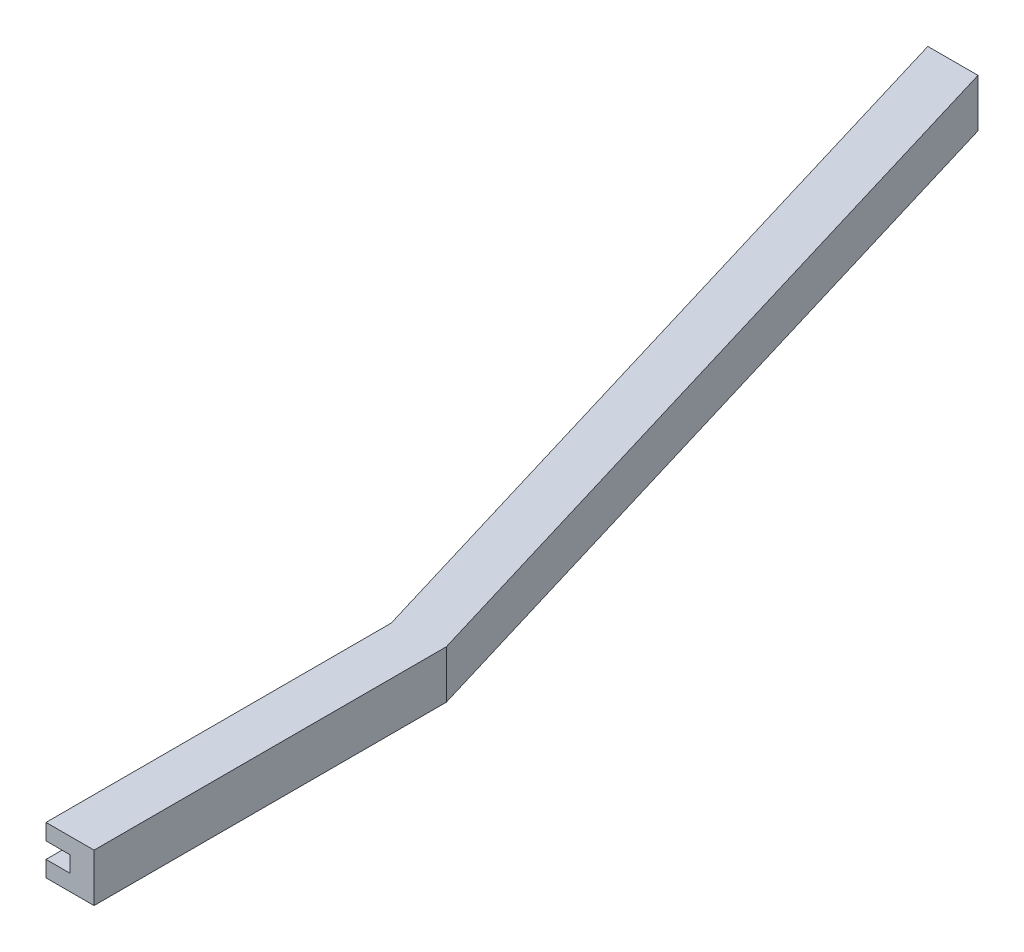
SolidWorks part; units mm, degrees
ref_plane "前视基准面" through (0, 0, 0) normal (0, 0, 1) x (1, 0, 0)
ref_plane "上视基准面" through (0, 0, 0) normal (0, 1, 0) x (1, 0, 0)
ref_plane "右视基准面" through (0, 0, 0) normal (1, 0, 0) x (0, 0, -1)
other "Configuration Table"
sketch "草图1" plane through (0, 0, 0) normal (0, 1, 0) x (1, 0, 0)
  line L0 (0, 0) -> (0, -73)
  line L1 (0, -73) -> (38.8, -73)
  line L2 (38.8, -73) -> (38.8, -47.5)
  line L3 (38.8, -47.5) -> (24.5, 0)
  line L4 (24.5, 0) -> (0, 0)
  dimension "D3" = 25.5
  dimension "D4" = 24.5
  dimension "D1" = 73
  dimension "D2" = 38.8
extrude "凸台-拉伸1" add sketch "草图1" along normal blind 3
sketch "草图2" plane through (0, 0, 0) normal (0, 0, -1) x (-1, 0, 0)
  line L0 (0.2, 0) -> (0.2, 3) construction
  line L1 (0, 0) -> (1.7, 0)
  line L2 (0, 0) -> (0, 3)
  line L3 (0, 3) -> (1.7, 3)
  line L4 (1.7, 0) -> (1.7, 3) construction
  circle A0 centre (1.7, 1.5) radius 1.5
  circle A1 centre (1.7, 1.5) radius 0.75
  line M10 (0, 0) -> (0, 3)
  dimension "D2" = 1.5
  dimension "D1" = 0.2
extrude "凸台-拉伸2" add sketch "草图2" against normal up to surface (73 mm away) contours A0 L3 L1 M10 | A0 A1 region at (-0.0345, 1.5, 0) region at (-0.2424, 1.5, 0) up to face at (19.4, 1.5, 73)
sketch "草图3" plane through (0, 3, 0) normal (0, 1, 0) x (1, 0, 0)
  line L0 (-1.7, -73) -> (38.8, -73) construction
  line L1 (38.8, -73) -> (-3.2, -73)
  line L2 (38.8, -73) -> (38.8, -69.5)
  line L3 (38.8, -69.5) -> (-3.2, -69.5)
  line L4 (-3.2, -73) -> (-3.2, -69.5)
  line L5 (38.8, -73) -> (38.8, -47.5) construction
  line L6 (-3.2, 0) -> (-3.2, -73) construction
  line L7 (-1.7, -73) -> (-1.7, 0) construction
  line L8 (0, -48.2) -> (-3.2, -48.2)
  line L9 (0, -48.2) -> (0, -28)
  line L10 (0, -28) -> (-3.2, -28)
  line L11 (-3.2, -48.2) -> (-3.2, -28)
  line L12 (-1.7, 0) -> (-3.2, 0) construction
  line L13 (1.3, -3) -> (22.2702, -3)
  line L14 (22.2702, -3) -> (35.8, -47.9418)
  line L15 (35.8, -47.9418) -> (35.8, -69.5)
  line L16 (35.8, -69.5) -> (1.3, -69.5)
  line L17 (1.3, -69.5) -> (1.3, -3)
  line L18 (38.8, -47.5) -> (24.5, 0) construction
  line L19 (24.5, 0) -> (-1.7, 0) construction
  dimension "D1" = 3.5
  dimension "D2" = 20.2
  dimension "D3" = 28
  dimension "D4" = 3
  dimension "D5" = 3
  dimension "D6" = 3
  dimension "D7" = 3
  dimension "D8" = 3.2
extrude "切除-拉伸1" cut sketch "草图3" against normal through all contours L17 L3 L15 L14 L13 | L11 L10 L9 L8 | L3 L4 L1 L2 region at (16.6038, 3, 39.0408)
sketch "草图4" plane through (1.3, 0, 0) normal (1, 0, 0) x (0, 0, -1)
  line L0 (-69.5, 0) -> (-69.5, 3) construction
  line L1 (-1.5, 1) -> (-69.5, 1)
  line L2 (-1.5, 1) -> (-1.5, 2)
  line L3 (-1.5, 2) -> (-69.5, 2)
  line L4 (-69.5, 1) -> (-69.5, 2)
  line L5 (-69.5, 0) -> (-47.5, 0) construction
  line L6 (-3, 0) -> (-3, 3) construction
  line L7 (-47.5, 2) -> (-47.5, 1)
  line L8 (-47.5, 3) -> (-47.5, 0) construction
  line M5 (-69.5, 3) -> (-69.5, 0)
  line M7 (-3, 0) -> (-3, 3)
  dimension "D1" = 1
  dimension "D2" = 1
  dimension "D3" = 1.5
extrude "切除-拉伸2" cut sketch "草图4" along normal offset from surface (24.0367 mm away) 1.5 from offset 1.5 contours L3 L7 L1 M7 region at (1.3, 1.5, 25.25) up to face at (29.0351, 1.5, 25.4709) offset beyond the face yes offset against normal yes
extrude "切除-拉伸3" cut sketch "草图4<3>" along normal offset from surface (37.5 mm away) 1.5 from offset 1.5 contours L7 L3 L1 M5 region at (1.3, 1.5, 58.5) up to face at (35.8, 1.5, 58.7209) offset beyond the face yes offset against normal yes
sketch "草图4<3>" plane through (1.3, 0, 0) normal (1, 0, 0) x (0, 0, -1) same geometry as "草图4"
sketch "草图5" plane through (35.8, 0, 0) normal (-1, 0, 0) x (0, 0, 1)
  line L0 (47.9418, 3) -> (69.5, 3) construction
  line L1 (47.9418, 3) -> (50.9418, 3)
  line L2 (47.9418, 3) -> (47.9418, 2)
  line L3 (47.9418, 2) -> (50.9418, 2)
  line L4 (50.9418, 3) -> (50.9418, 2)
  line L5 (47.9418, 2) -> (69.5, 2) construction
  line L6 (47.9418, 2) -> (47.9418, 3) construction
  dimension "D1" = 3
extrude "凸台-拉伸3" add sketch "草图5" along normal up to surface (34.5 mm away) up to face at (1.3, 2.5, 36.25)
sketch "草图6" plane through (0, 3, 0) normal (0, 1, 0) x (1, 0, 0)
  line L0 (35.8, -50.9418) -> (35.8, -47.9418) construction
  line L1 (35.8, -50.9418) -> (35.8, -69.5) construction
  line L2 (1.3, -50.9418) -> (35.8, -50.9418) construction
  line L3 (1.3, -47.9418) -> (35.8, -47.9418) construction
  circle A0 centre (32.8, -49.4418) radius 0.35
  circle A1 centre (24.9, -49.4418) radius 0.35
  point P14 (35.8, -49.4418)
  dimension "D1" = 0.7
  dimension "D2" = 7.9
  dimension "D3" = 3
extrude "切除-拉伸4" cut sketch "草图6" against normal through all
sketch "草图7" plane through (0, 0, 3) normal (0, 0, 1) x (1, 0, 0)
  line L0 (-0.2, 2) -> (-0.2, 1) construction
  line L1 (-0.2, 2) -> (23.8367, 2)
  line L2 (-0.2, 2) -> (-0.2, 1)
  line L3 (-0.2, 1) -> (23.8367, 1)
  line L4 (23.8367, 2) -> (23.8367, 1)
  line L5 (22.2702, 1) -> (35.8, 1) construction
  line L6 (1.3, 2) -> (35.8, 2) construction
  line L7 (23.8367, 2) -> (23.8367, 1) construction
extrude "切除-拉伸5" cut sketch "草图7" against normal blind 1.5
sketch "草图8" plane through (0, 3, 0) normal (0, 1, 0) x (1, 0, 0)
  line L0 (20.3324, 3.4367) -> (35.8, -47.9418)
  line L1 (35.8, -47.9418) -> (35.8, -72.8495)
  line L2 (35.8, -72.8495) -> (56.308, -72.8495)
  line L3 (56.308, -72.8495) -> (56.308, 3.4367)
  line L4 (56.308, 3.4367) -> (20.3324, 3.4367)
  line L5 (22.2702, -3) -> (35.8, -47.9418) construction
extrude "切除-拉伸6" cut sketch "草图8" against normal through all flip side to cut
